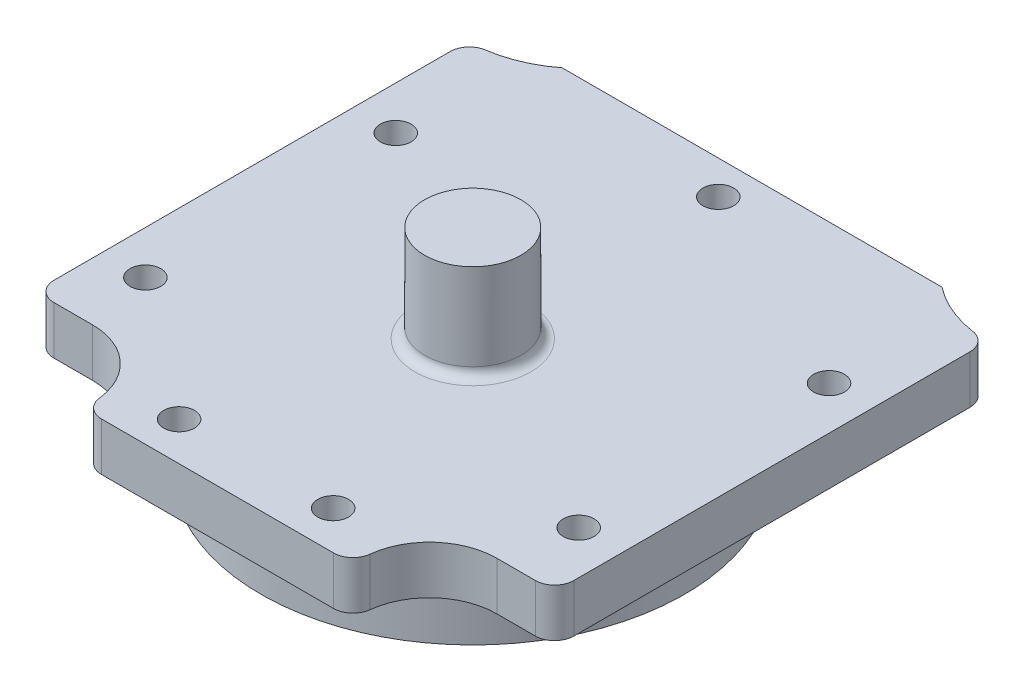
SolidWorks part; units mm, degrees
material "Резина"
ref_plane "Спереди" through (0, 0, 0) normal (0, 0, 1) x (1, 0, 0)
ref_plane "Сверху" through (0, 0, 0) normal (0, 1, 0) x (1, 0, 0)
ref_plane "Справа" through (0, 0, 0) normal (1, 0, 0) x (0, 0, -1)
ref_plane "Плоскость4" through (0, -2, 0) normal (0, -1, 0) x (-1, 0, 0)
sketch "Эскиз1" plane through (0, -2, 0) normal (0, -1, 0) x (-1, 0, 0)
  line L4 (11, -50.5) -> (11, -9.3545)
  line L5 (3.7313, -5) -> (-35.7313, -5)
  line L6 (-43, -9.3545) -> (-43, -50.5)
  line L7 (-28.0557, -60.5) -> (-3.9443, -60.5)
  line L8 (11, -50.5) -> (11, -9.3545)
  line L9 (3.7313, -5) -> (-35.7313, -5)
  line L10 (-43, -9.3545) -> (-43, -50.5)
  line L11 (-28.0557, -60.5) -> (-3.9443, -60.5)
  line L40 (-41, -52.5) -> (-37, -52.5)
  line L41 (-41, -52.5) -> (-37, -52.5)
  line L46 (5, -52.5) -> (9, -52.5)
  line L47 (5, -52.5) -> (9, -52.5)
  circle A0 centre (-38.5, -45.5) radius 1.6 construction
  circle A1 centre (-38.5, -19.5) radius 1.6 construction
  circle A2 centre (-16, -8.5) radius 1.6 construction
  circle A3 centre (6.5, -45.5) radius 1.6 construction
  circle A4 centre (6.5, -19.5) radius 1.6 construction
  circle A5 centre (-38.5, -45.5) radius 1.6
  circle A6 centre (-38.5, -19.5) radius 1.6
  circle A7 centre (-24, -56.5) radius 1.6 construction
  circle A8 centre (6.5, -45.5) radius 1.6
  circle A9 centre (6.5, -19.5) radius 1.6
  arc A10 (-30.0433, -58.7222) -> (-37, -52.5) centre (-37, -59.5) ccw
  arc A11 (3.7313, -5) -> (9.2895, -7.3755) centre (11, 4.3167) ccw
  arc A12 (-41.2895, -7.3755) -> (-35.7313, -5) centre (-43, 4.3167) ccw
  arc A13 (-30.0433, -58.7222) -> (-37, -52.5) centre (-37, -59.5) ccw
  arc A14 (5, -52.5) -> (-1.9567, -58.7222) centre (5, -59.5) ccw
  arc A15 (5, -52.5) -> (-1.9567, -58.7222) centre (5, -59.5) ccw
  circle A16 centre (-16, -8.5) radius 1.6
  arc A21 (3.7313, -5) -> (9.2895, -7.3755) centre (11, 4.3167) ccw
  arc A22 (-41.2895, -7.3755) -> (-35.7313, -5) centre (-43, 4.3167) ccw
  circle A53 centre (-24, -56.5) radius 1.6
  circle A54 centre (-8, -56.5) radius 1.6 construction
  circle A55 centre (-8, -56.5) radius 1.6
  arc A96 (11, -9.3545) -> (9.2895, -7.3755) centre (9, -9.3545) ccw
  arc A97 (11, -9.3545) -> (9.2895, -7.3755) centre (9, -9.3545) ccw
  arc A98 (-41.2895, -7.3755) -> (-43, -9.3545) centre (-41, -9.3545) ccw
  arc A99 (-41.2895, -7.3755) -> (-43, -9.3545) centre (-41, -9.3545) ccw
  arc A100 (-43, -50.5) -> (-41, -52.5) centre (-41, -50.5) ccw
  arc A101 (-43, -50.5) -> (-41, -52.5) centre (-41, -50.5) ccw
  arc A102 (-30.0433, -58.7222) -> (-28.0557, -60.5) centre (-28.0557, -58.5) ccw
  arc A103 (-30.0433, -58.7222) -> (-28.0557, -60.5) centre (-28.0557, -58.5) ccw
  arc A104 (-3.9443, -60.5) -> (-1.9567, -58.7222) centre (-3.9443, -58.5) ccw
  arc A105 (-3.9443, -60.5) -> (-1.9567, -58.7222) centre (-3.9443, -58.5) ccw
  arc A106 (9, -52.5) -> (11, -50.5) centre (9, -50.5) ccw
  arc A107 (9, -52.5) -> (11, -50.5) centre (9, -50.5) ccw
  dimension "D1" = 0
extrude "Бобышка-Вытянуть1" add sketch "Эскиз1" along normal blind 5
sketch "Эскиз2" plane through (0, -2, 0) normal (0, 1, 0) x (1, 0, 0)
  circle A0 centre (16, -34) radius 5 construction
  circle A1 centre (16, -34) radius 5
extrude "Бобышка-Вытянуть2" add sketch "Эскиз2" along normal blind 10
fillet "Скругление1" radius 1 1 edges at (16, -2, 29)
sketch "Эскиз3" plane through (0, -7, 0) normal (0, -1, 0) x (1, 0, 0)
  circle A0 centre (16, 34) radius 5 construction
  circle A1 centre (16, 34) radius 5 construction
  circle A4 centre (16, 34) radius 22
  dimension "D2" = 44
extrude "Бобышка-Вытянуть3" add sketch "Эскиз3" along normal blind 7 contours A4
sketch "Эскиз4" plane through (0, -14, 0) normal (0, -1, 0) x (1, 0, 0)
  circle A0 centre (16, 34) radius 22 construction
  circle A1 centre (16, 34) radius 22 construction
  circle A2 centre (16, 34) radius 14
  circle A3 centre (16, 34) radius 19
  dimension "D1" = 28
  dimension "D2" = 38
extrude "Вырез-Вытянуть1" cut sketch "Эскиз4" against normal blind 7
sketch "Эскиз5" plane through (0, 0, 5) normal (0, 0, -1) x (-1, 0, 0)
  line L0 (-16, -2) -> (-16, -7) construction
  line L1 (3.7313, -2) -> (-35.7313, -2) construction
  line L2 (3.7313, -7) -> (-35.7313, -7) construction
ref_plane "Плоскость5" through (16, 0, 0) normal (1, 0, 0) x (0, -1, 0)
sketch "Эскиз6" plane through (16, 0, 0) normal (1, 0, 0) x (0, -1, 0)
  line L0 (7, -16) -> (14, -15)
  line L1 (14, -53) -> (14, -15) construction
  line L2 (14, -53) -> (14, -15) construction
  line L3 (14, -48) -> (14, -20) construction
  line L4 (14, -48) -> (14, -20) construction
  line L5 (14, -34) -> (7, -34) construction
  line L6 (7, -48) -> (7, -20) construction
  line L7 (7, -48) -> (7, -20) construction
  line L8 (7, -20) -> (7, -15) construction
  line L11 (7, -19) -> (14, -20)
  line L12 (14, -20) -> (7, -20)
  line L13 (7, -20) -> (7, -19)
  line L14 (14, -15) -> (7, -15)
  line L15 (7, -15) -> (7, -16)
  dimension "D1" = 15
  dimension "D2" = 18
revolve "Повернуть1" add sketch "Эскиз6" angle 360 about L5
fillet "Скругление2" radius 1 1 edges at (16, -7, 12)
